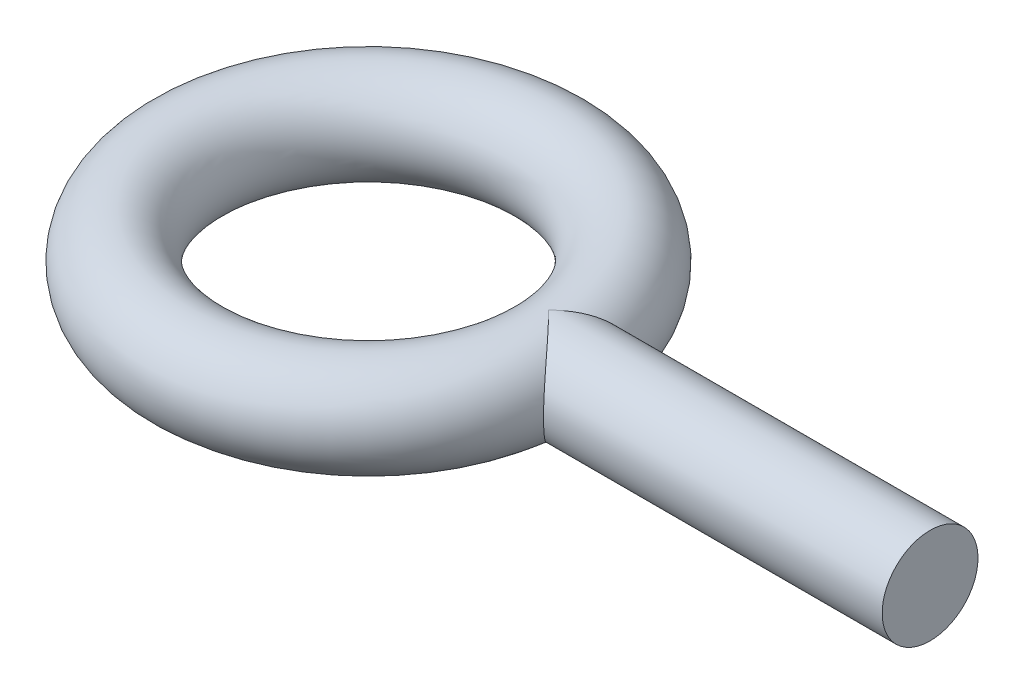
SolidWorks part; units mm, degrees
ref_plane "Front Plane" through (0, 0, 0) normal (0, 0, 1) x (1, 0, 0)
ref_plane "Top Plane" through (0, 0, 0) normal (0, 1, 0) x (1, 0, 0)
ref_plane "Right Plane" through (0, 0, 0) normal (1, 0, 0) x (0, 0, -1)
sketch "layout" plane through (0, 0, 0) normal (0, 1, 0) x (1, 0, 0)
  line L0 (0, 0) -> (37.211, 0) construction
  circle A0 centre (0, 0) radius 15.113 construction
  dimension "D1" = 30.226
  dimension "D2" = 52.324
sketch "Sketch2" plane through (0, 0, 0) normal (0, 0, 1) x (1, 0, 0)
  line L3 (0, 0) -> (0, 6.6909) construction
  line L4 (15.113, 0) -> (-15.113, 0) construction
  circle A0 centre (-11.938, 0) radius 3.175
  point P4 (-15.113, 0)
  dimension "D1" = 6.35
revolve "Revolve1" add sketch "Sketch2" angle 360 about L3
ref_plane "Plane1" through (37.211, 0, 0) normal (1, 0, 0) x (0, 0, -1)
sketch "Sketch3" plane through (37.211, 0, 0) normal (1, 0, 0) x (0, 0, -1)
  circle A0 centre (0, 0) radius 3.175
extrude "Extrude1" add sketch "Sketch3" against normal up to next
cosmetic thread "Cosmetic Thread1" [suppressed] parameters "D1"=19.05, "D2"=4.7625
sketch "Sketch4" plane through (0, 0, 0) normal (0, 1, 0) x (1, 0, 0)
  line L0 (36.7527, 3.175) -> (37.211, 2.3812)
  line L1 (37.211, 2.3812) -> (37.6693, 3.175)
  line L2 (37.6693, 3.175) -> (37.6693, 4.0915)
  line L3 (37.6693, 4.0915) -> (36.7527, 4.0915)
  line L4 (36.7527, 4.0915) -> (36.7527, 3.175)
  line L5 (0, 0) -> (42.1538, 0) construction
  dimension "D1" = 4.7625
  dimension "D2" = 6.35
revolve "Cut-Revolve1" [suppressed] cut sketch "Sketch4" angle 360 about L5
pattern_linear "LPattern1" [suppressed] count 15 along (-1, 0, 0) of bodies 103
equation "\"A@Sketch3\" = \"D1@Sketch2\""
equation "\"D1@Sketch4\" = \"D2@Cosmetic Thread1\""
equation "\"D2@Sketch4\" = \"D1@Sketch2\""
equation "\"D1@LPattern1\" = \"D1@Cosmetic Thread1\" / \"p@LPattern1\""
